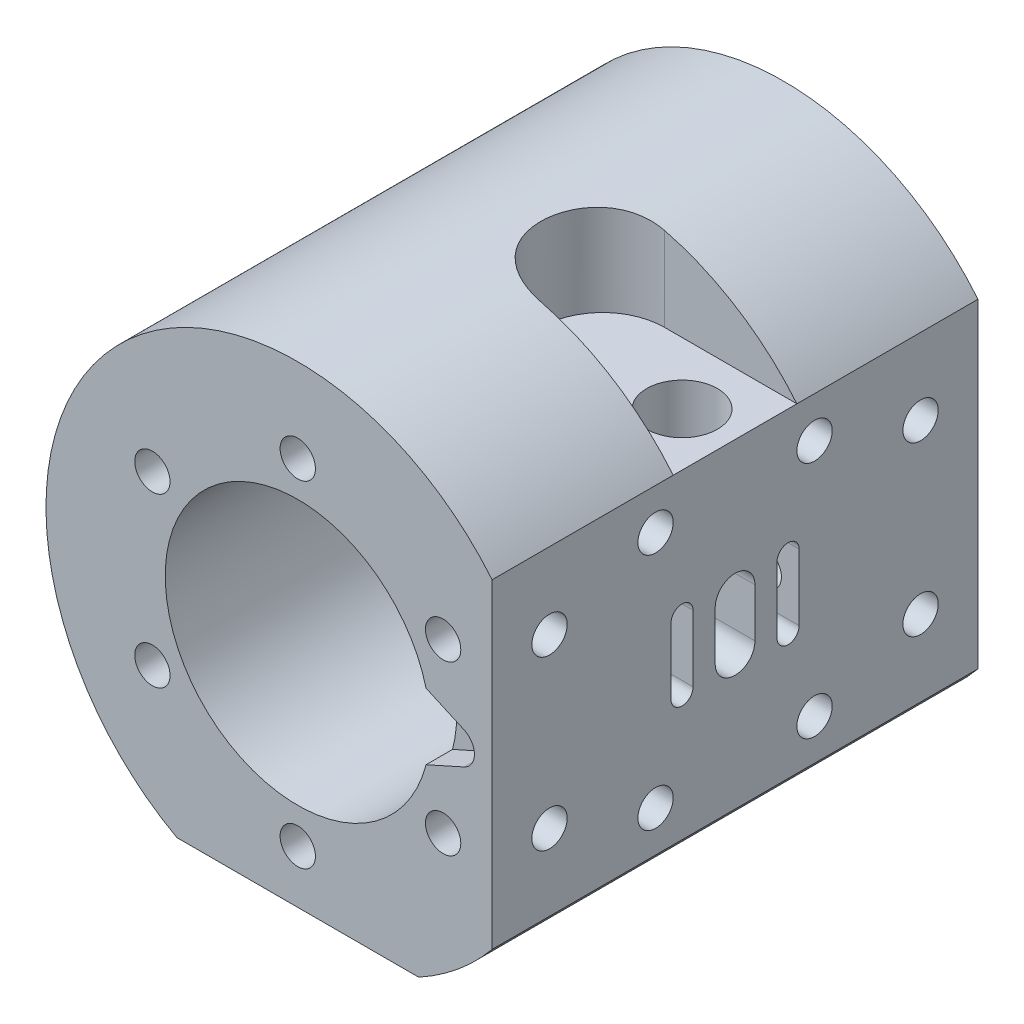
SolidWorks part; units mm, degrees
material "Alumina"
ref_plane "Front Plane" through (0, 0, 0) normal (0, 0, 1) x (1, 0, 0)
ref_plane "Top Plane" through (0, 0, 0) normal (0, 1, 0) x (1, 0, 0)
ref_plane "Right Plane" through (0, 0, 0) normal (1, 0, 0) x (0, 0, -1)
sketch "Sketch1" plane through (0, 0, 0) normal (0, 0, 1) x (1, 0, 0)
  line L0 (22, 18.1177) -> (22, -18.1177)
  line L1 (13.6839, -25) -> (-13.6839, -25)
  arc A0 (22, 18.1177) -> (-13.6839, -25) centre (0, 0) ccw
  circle A1 centre (0, 0) radius 15
  arc A4 (13.6839, -25) -> (22, -18.1177) centre (0, 0) ccw
  dimension "D1" = 57
  dimension "D2" = 30
  dimension "D5" = 22
  dimension "D6" = 25
extrude "Boss-Extrude1" add sketch "Sketch1" along normal mid plane 55 contours L1 A4 L0 A0 A1 region at (21.2643, 0, 0)
sketch "Sketch2" plane through (0, 0, 27.5) normal (0, 0, 1) x (1, 0, 0)
  line L0 (18.8181, 1.825) -> (14.5237, 3.75)
  line L1 (14.5237, -3.75) -> (18.8181, -1.825)
  circle A0 centre (0, 0) radius 19 construction
  circle A1 centre (0, 19) radius 2
  circle A2 centre (16.4545, 9.5) radius 2
  circle A3 centre (16.4545, -9.5) radius 2
  circle A4 centre (0, -19) radius 2
  circle A5 centre (-16.4545, -9.5) radius 2
  circle A6 centre (-16.4545, 9.5) radius 2
  circle A7 centre (18, 0) radius 2
  circle A8 centre (0, 0) radius 15 construction
  arc A9 (14.5237, -3.75) -> (14.5237, 3.75) centre (0, 0) ccw
  point P17 (0, 0)
  circle M1 centre (0, 0) radius 15
  dimension "D1" = 4
  dimension "38" = 38
  dimension "D3" = 4
  dimension "D4" = 7.5
  dimension "D5" = 18
  dimension "D2" = 6
extrude "Cut-Extrude1" cut sketch "Sketch2<5>" against normal blind 10 contours A1 | A6 | A5 | A3 | A2 | A4 region at (0, 19, 27.5) region at (16.4545, 9.5, 27.5) region at (16.4545, -9.5, 27.5) region at (0, -19, 27.5) region at (-16.4545, -9.5, 27.5) region at (-16.4545, 9.5, 27.5)
sketch "Sketch2<5>" plane through (0, 0, 27.5) normal (0, 0, 1) x (1, 0, 0) same geometry as "Sketch2"
cosmetic thread "Cosmetic Thread1" parameters "D2"=5
cosmetic thread "Cosmetic Thread2" parameters "D2"=5
cosmetic thread "Cosmetic Thread3" parameters "D2"=5
cosmetic thread "Cosmetic Thread4" parameters "D2"=5
cosmetic thread "Cosmetic Thread5" parameters "D2"=5
cosmetic thread "Cosmetic Thread6" parameters "D2"=5
extrude "Cut-Extrude2" cut sketch "Sketch2<3>" against normal blind 3 contours A7 L0 L1 M1 region at (15.8632, 0, 27.5)
sketch "Sketch2<3>" plane through (0, 0, 27.5) normal (0, 0, 1) x (1, 0, 0) same geometry as "Sketch2"
ref_plane "Plane1" through (0, 18.1177, 0) normal (0, 1, 0) x (1, 0, 0)
sketch "Sketch3" plane through (0, 18.1177, 0) normal (0, 1, 0) x (1, 0, 0)
  line L0 (0, 0) -> (50000, 0) construction
  line L1 (22, 7) -> (22, -7)
  line L2 (22, -27.5) -> (22, 27.5) construction
  line L3 (22, -7) -> (7, -7)
  line L4 (22, 7) -> (7, 7)
  arc A0 (7, 7) -> (7, -7) centre (7, 0) ccw
  point P7 (22, 0)
  point P16 (0, 0)
  dimension "D1" = 22
  dimension "14" = 14
extrude "Cut-Extrude3" cut sketch "Sketch3" along normal up to next
sketch "Sketch4" plane through (22, 0, 0) normal (1, 0, 0) x (0, 0, -1)
  line L0 (0, 0) -> (0, -50000) construction
  line L1 (0, 0) -> (-50000, 0) construction
  line L2 (0, 2.75) -> (0, -2.75) construction
  line L3 (2.25, 2.75) -> (2.25, -2.75)
  line L4 (-2.25, 2.75) -> (-2.25, -2.75)
  line L5 (-6, 3.75) -> (-6, -3.75) construction
  line L6 (-4.75, 3.75) -> (-4.75, -3.75)
  line L7 (-7.25, 3.75) -> (-7.25, -3.75)
  line L8 (0, 5) -> (-39.7422, 5) construction
  line L9 (0, -5) -> (-39.7422, -5) construction
  line L11 (6, 3.75) -> (6, -3.75) construction
  line L12 (4.75, 3.75) -> (4.75, -3.75)
  line L13 (7.25, 3.75) -> (7.25, -3.75)
  circle A0 centre (-9, 13.5) radius 2
  circle A1 centre (-21, 9.5) radius 2
  circle A2 centre (9, 13.5) radius 2
  circle A3 centre (21, 9.5) radius 2
  circle A4 centre (21, -9.5) radius 2
  circle A5 centre (9, -13.5) radius 2
  circle A6 centre (-9, -13.5) radius 2
  circle A7 centre (-21, -9.5) radius 2
  arc A8 (2.25, 2.75) -> (-2.25, 2.75) centre (0, 2.75) ccw
  arc A9 (-2.25, -2.75) -> (2.25, -2.75) centre (0, -2.75) ccw
  arc A10 (-4.75, 3.75) -> (-7.25, 3.75) centre (-6, 3.75) ccw
  arc A11 (-7.25, -3.75) -> (-4.75, -3.75) centre (-6, -3.75) ccw
  arc A12 (4.75, 3.75) -> (7.25, 3.75) centre (6, 3.75) cw
  arc A13 (7.25, -3.75) -> (4.75, -3.75) centre (6, -3.75) cw
  point P11 (0, 0)
  point P30 (-6, 0)
  point P51 (6, 0)
  dimension "D1" = 4
  dimension "D2" = 9
  dimension "D3" = 13.5
  dimension "D4" = 9.5
  dimension "D5" = 21
  dimension "D6" = 10
  dimension "D7" = 2.5
  dimension "2.5" = 2.5
  dimension "5" = 4.5
extrude "Cut-Extrude4" cut sketch "Sketch4" against normal blind 10 contours A1 | A0 | A2 | A3 | A4 | A5 | A6 | A7 region at (22, 13.5, 9) region at (22, 9.5, 21) region at (22, 13.5, -9) region at (22, 9.5, -21) region at (22, -9.5, -21) region at (22, -13.5, -9) region at (22, -13.5, 9) region at (22, -9.5, 21)
cosmetic thread "Cosmetic Thread7" parameters "D2"=5
cosmetic thread "Cosmetic Thread8" parameters "D2"=5
cosmetic thread "Cosmetic Thread9" parameters "D2"=5
cosmetic thread "Cosmetic Thread10" parameters "D2"=5
cosmetic thread "Cosmetic Thread11" parameters "D2"=5
cosmetic thread "Cosmetic Thread12" parameters "D2"=5
cosmetic thread "Cosmetic Thread13" parameters "D2"=5
cosmetic thread "Cosmetic Thread14" parameters "D2"=5
extrude "Cut-Extrude5" cut sketch "Sketch4<3>" against normal up to next contours L7 A11 L6 A10 | L4 A9 L3 A8 | A13 L13 A12 L12 region at (22, 0, 0) region at (22, 0, 6) region at (22, 0, -6)
sketch "Sketch4<3>" plane through (22, 0, 0) normal (1, 0, 0) x (0, 0, -1) same geometry as "Sketch4"
extrude "Cut-Extrude6" cut sketch "Sketch2" against normal up to next contours A7 region at (18, 0, 27.5)
sketch "Sketch5" plane through (0, -25, 0) normal (0, -1, 0) x (1, 0, 0)
  line L0 (0, 0) -> (0, -50000) construction
  line L1 (0, 0) -> (50000, 0) construction
  circle A0 centre (0, 15) radius 3
  circle A1 centre (0, -15) radius 3
  dimension "D1" = 6
  dimension "D2" = 15
extrude "Cut-Extrude7" cut sketch "Sketch5" against normal blind 6
cosmetic thread "Cosmetic Thread15" parameters "D2"=8
cosmetic thread "Cosmetic Thread16" parameters "D2"=8
sketch "Sketch8" plane through (0, 0, 0) normal (0, 0, 1) x (1, 0, 0)
  line L0 (16, 18.1177) -> (16, -49981.8823) construction
  line L2 (22, 18.1177) -> (22, -18.1177) construction
  line L3 (16, 18.1177) -> (20, 18.1177)
  line L4 (20, 18.1177) -> (20, 11.1177)
  line L5 (20, 11.1177) -> (18.25, 10.1177)
  line L6 (18.25, 10.1177) -> (18.25, 3.0469)
  line L10 (7, 18.1177) -> (22, 18.1177) construction
  line L11 (7, 18.1177) -> (22, 18.1177) construction
  line L12 (16, 3.0469) -> (16, 18.1177)
  line L13 (18.25, 3.0469) -> (16, 3.0469)
  dimension "D1" = 6
  dimension "D2" = 8
  dimension "D3" = 4.5
  dimension "D4" = 8
  dimension "D6" = 1
revolve "Cut-Revolve1" cut sketch "Sketch8" angle 360 about L0
cosmetic thread "Cosmetic Thread17" parameters "D2"=10
mirror "Mirror1" about plane through (0, 0, 0) normal (0, 0, 1) of "Cut-Extrude6", "Cut-Extrude2", "Cut-Extrude1"
cosmetic thread "Cosmetic Thread18" parameters "D2"=5
cosmetic thread "Cosmetic Thread19" parameters "D2"=5
cosmetic thread "Cosmetic Thread20" parameters "D2"=5
cosmetic thread "Cosmetic Thread21" parameters "D2"=5
